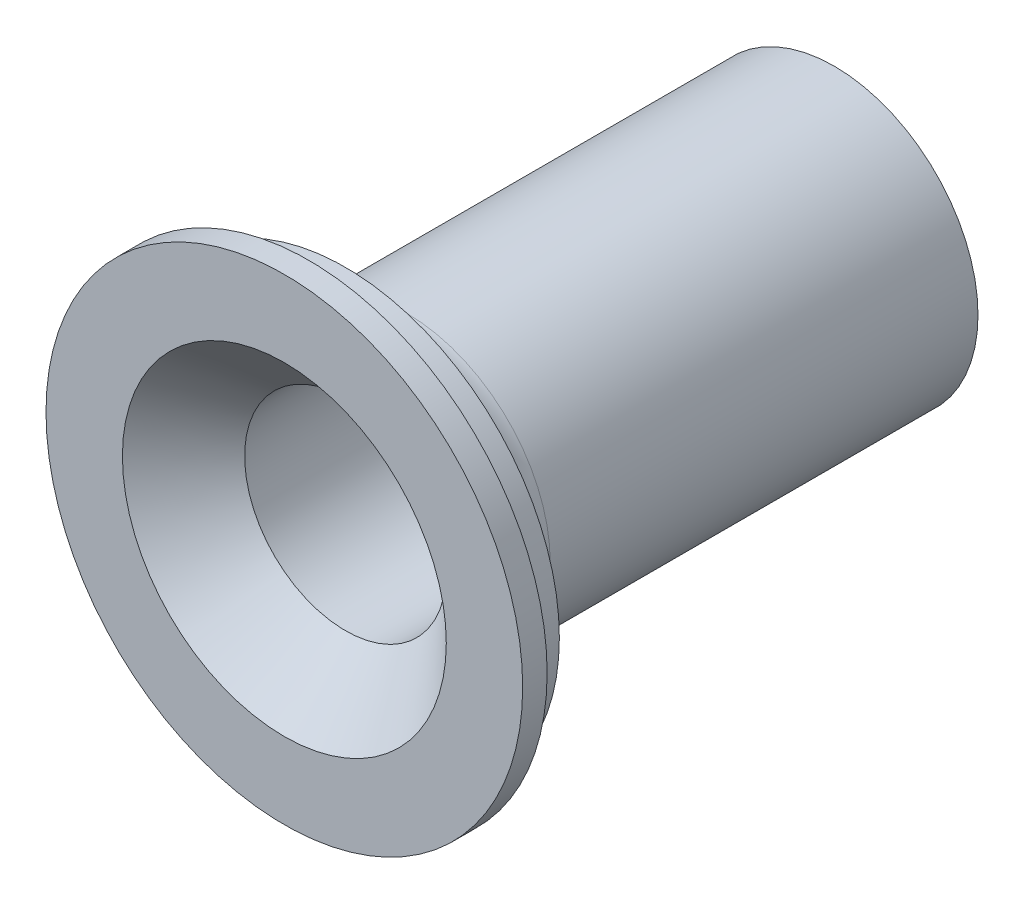
SolidWorks part; units mm, degrees
material "ABS"
ref_plane "Front" through (0, 0, 0) normal (0, 0, 1) x (1, 0, 0)
ref_plane "Top" through (0, 0, 0) normal (0, 1, 0) x (1, 0, 0)
ref_plane "Right" through (0, 0, 0) normal (1, 0, 0) x (0, 0, -1)
sketch "Szkic1" plane through (0, 0, 0) normal (0, 1, 0) x (1, 0, 0)
  line L14 (0, 0) -> (0, 46) construction
  line L15 (8.25, 5) -> (13.25, 0)
  line L16 (8.25, 35) -> (8.25, 5)
  line L17 (19.5, 0) -> (13.25, 0)
  line L18 (11.75, 45) -> (11.75, 10)
  line L19 (17.5, 5) -> (16.75, 5)
  line L20 (17.5, 5) -> (17.5, 2)
  line L21 (17.5, 2) -> (19.5, 2)
  line L22 (19.5, 2) -> (19.5, 0)
  line L23 (2, 45) -> (2, 38)
  line L24 (5.25, 38) -> (2, 38)
  line L25 (11.75, 45) -> (2, 45)
  arc A2 (11.75, 10) -> (16.75, 5) centre (16.75, 10) ccw
  arc A3 (8.25, 35) -> (5.25, 38) centre (5.25, 35) ccw
revolve "Obrót1" add sketch "Szkic1" angle 360 about L14
sketch "Szkic2" plane through (0, 0, -45) normal (0, 0, -1) x (-1, 0, 0)
  line L1 (0, -8.0829) -> (7, -4.0415)
  line L2 (7, -4.0415) -> (7, 4.0415)
  line L3 (7, 4.0415) -> (0, 8.0829)
  line L4 (0, 8.0829) -> (-7, 4.0415)
  line L5 (-7, 4.0415) -> (-7, -4.0415)
  line L6 (-7, -4.0415) -> (0, -8.0829)
  circle A0 centre (0, 0) radius 7 construction
  circle A1 centre (0, 0) radius 2
  dimension "D1" = 14
extrude "Dodanie-wyciągnięcie1" add sketch "Szkic2" along normal blind 1
